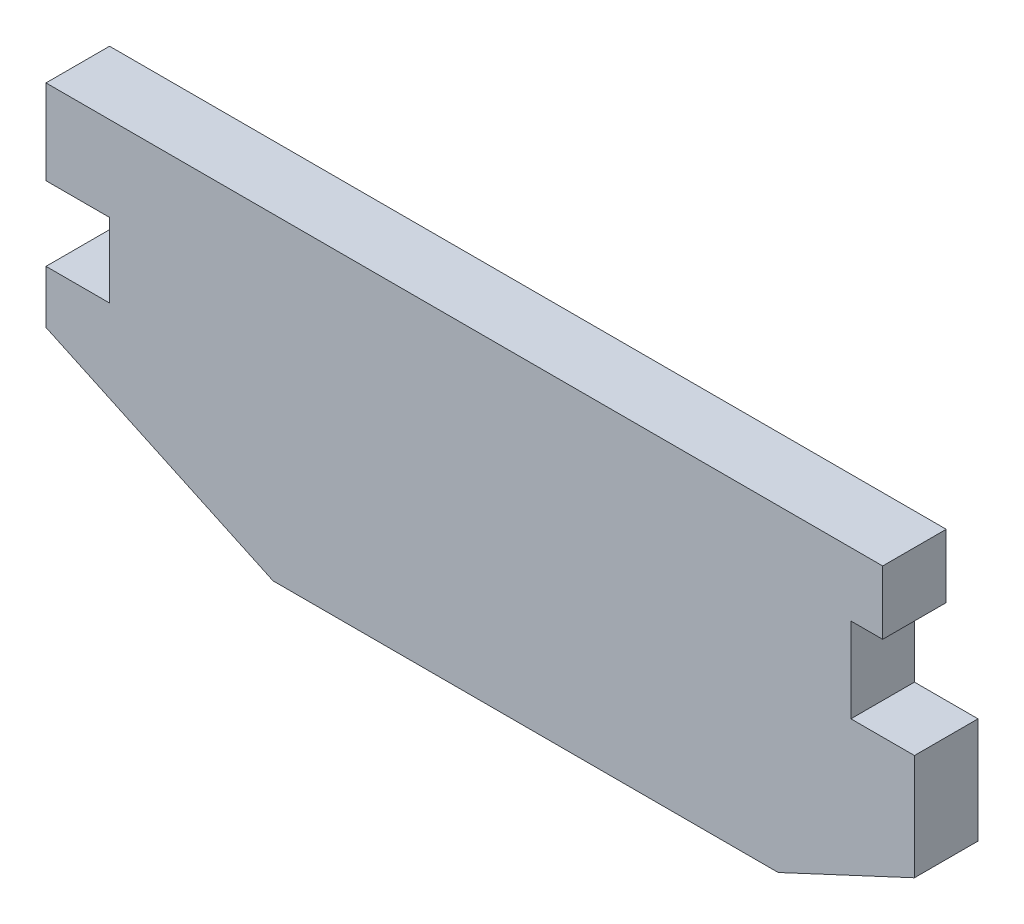
SolidWorks part; units mm, degrees
material "Plywood"
ref_plane "Plan de face" through (0, 0, 0) normal (0, 0, 1) x (1, 0, 0)
ref_plane "Plan de dessus" through (0, 0, 0) normal (0, 1, 0) x (1, 0, 0)
ref_plane "Plan de droite" through (0, 0, 0) normal (1, 0, 0) x (0, 0, -1)
sketch "Esquisse1" plane through (0, 0, 0) normal (0, 0, 1) x (1, 0, 0)
  line L1 (0, 0) -> (82, 0)
  line L2 (0, 0) -> (0, 30)
  line L3 (0, 30) -> (82, 30)
  line L4 (82, 0) -> (82, 30)
  dimension "D1" = 30
  dimension "D2" = 82
extrude "Boss.-Extru.1" add sketch "Esquisse1" along normal blind 6
sketch "Esquisse2" plane through (0, 0, 6) normal (0, 0, 1) x (1, 0, 0)
  line L0 (82, 30) -> (79, 30)
  line L1 (82, 30) -> (0, 30) construction
  line L2 (79, 30) -> (79, 24)
  line L3 (79, 24) -> (76, 24)
  line L4 (76, 24) -> (76, 16)
  line L5 (76, 16) -> (82, 16)
  line L6 (82, 0) -> (82, 30) construction
  line L7 (82, 16) -> (82, 30)
  dimension "D1" = 3
  dimension "D2" = 3
  dimension "D3" = 6
  dimension "D4" = 8
extrude "Enlèv. mat.-Extru.1" cut sketch "Esquisse2" against normal blind 10
sketch "Esquisse3" plane through (0, 0, 6) normal (0, 0, 1) x (1, 0, 0)
  line L0 (0, 30) -> (0, 0) construction
  line L1 (0, 22) -> (6, 22)
  line L2 (0, 22) -> (0, 15)
  line L3 (0, 15) -> (6, 15)
  line L4 (6, 22) -> (6, 15)
  line L5 (79, 30) -> (0, 30) construction
  dimension "D1" = 6
  dimension "D2" = 7
  dimension "D3" = 8
extrude "Enlèv. mat.-Extru.2" cut sketch "Esquisse3" against normal through all
chamfer "Chanfrein1" distance 10 angle 65 1 edges at (0, 0, 3) first distance on face at (0, 7.5, 3)
chamfer "Chanfrein2" distance 6 angle 65 1 edges at (82, 0, 3) first distance on face at (82, 8, 3)
